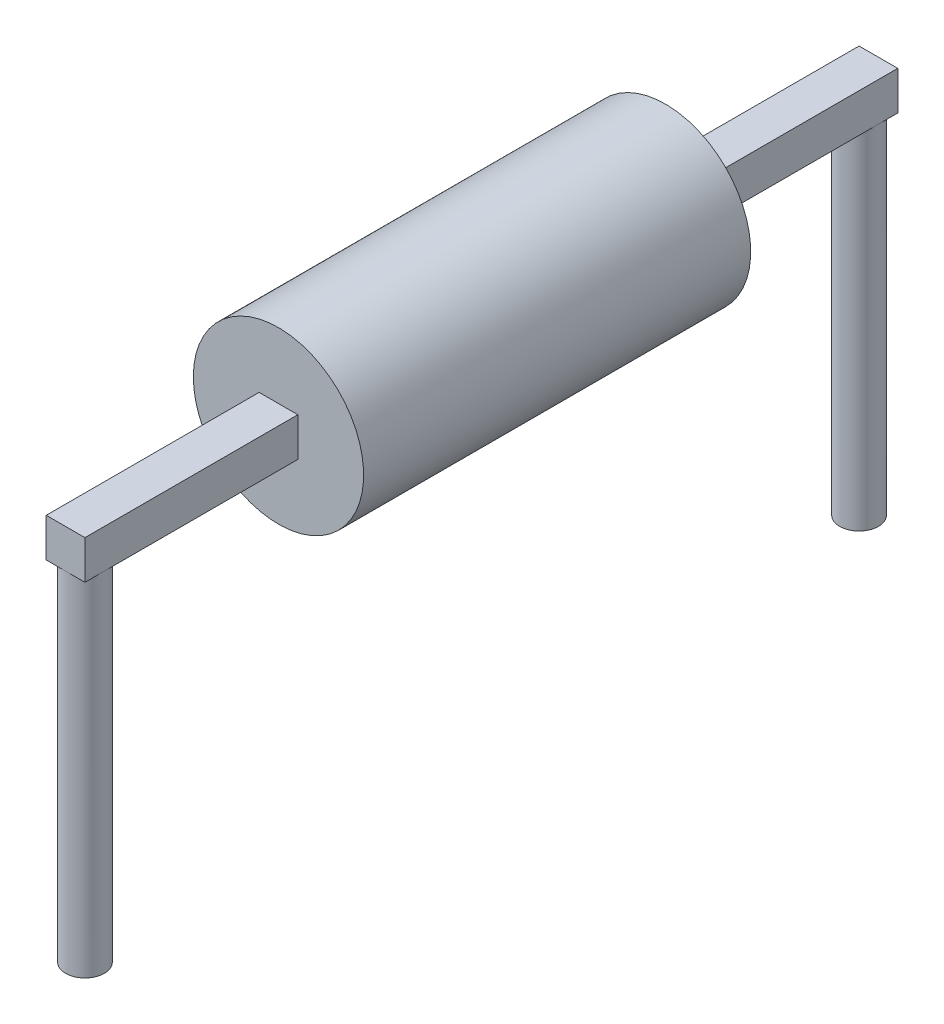
SolidWorks part; units mm, degrees
ref_plane "Спереди" through (0, 0, 0) normal (0, 0, 1) x (1, 0, 0)
ref_plane "Сверху" through (0, 0, 0) normal (0, 1, 0) x (1, 0, 0)
ref_plane "Справа" through (0, 0, 0) normal (1, 0, 0) x (0, 0, -1)
sketch "Эскиз1" plane through (0, 0, 0) normal (0, 0, 1) x (1, 0, 0)
  circle A0 centre (0, 0) radius 1.1
  dimension "D1" = 2.2
extrude "Вытянуть1" add sketch "Эскиз1" along normal blind 5
sketch "Эскиз2" plane through (0, 0, 5) normal (0, 0, 1) x (1, 0, 0)
  line L0 (-0.0001, 0.6747) -> (-0.0001, -0.3959) construction
  line L1 (-0.2501, -0.25) -> (0.2499, -0.25)
  line L2 (-0.2501, -0.25) -> (-0.2501, 0.25)
  line L3 (-0.2501, 0.25) -> (0.2499, 0.25)
  line L4 (0.2499, -0.25) -> (0.2499, 0.25)
  line L5 (-0.474, 0) -> (0.6636, 0) construction
  dimension "D2" = 0.5
extrude "Вытянуть2" add sketch "Эскиз2" along normal blind 2.75 and the other way blind 7.75
sketch "Эскиз3" plane through (0, -0.25, 0) normal (0, -1, 0) x (1, 0, 0)
  line L0 (0, 5) -> (0, 0) construction
  line L1 (-0.2501, 7.75) -> (0.2499, 7.75) construction
  line L2 (-0.2501, -2.75) -> (0.2499, -2.75) construction
  circle A0 centre (0, 7.5) radius 0.25
  circle A1 centre (0, -2.5) radius 0.25
  dimension "D1" = 0.5
extrude "Вытянуть3" add sketch "Эскиз3" along normal blind 4.5
